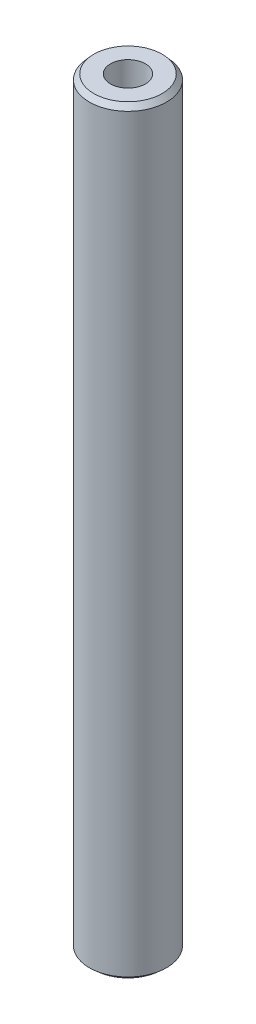
SolidWorks part; units mm, degrees
ref_plane "Front Plane" through (0, 0, 0) normal (0, 0, 1) x (1, 0, 0)
ref_plane "Top Plane" through (0, 0, 0) normal (0, 1, 0) x (1, 0, 0)
ref_plane "Right Plane" through (0, 0, 0) normal (1, 0, 0) x (0, 0, -1)
sketch "Sketch1" plane through (0, 0, 0) normal (0, 1, 0) x (1, 0, 0)
  circle A0 centre (0, 0) radius 5
  dimension "SHAFT_OD" = 10
extrude "Boss-Extrude1" add sketch "Sketch1" along normal blind 98.2793
sketch "Sketch2" plane through (0, 0, 0) normal (0, 1, 0) x (1, 0, 0)
  circle A0 centre (0, 0) radius 2.2611
  dimension "BORE_D" = 4.5222
extrude "Cut-Extrude1" cut sketch "Sketch2" along normal through all
chamfer "Chamfer1" distance 0.663 angle 41.206 2 edges at (0, 98.2793, 5) (0, 0, 5) first distance on face at (0, 98.2793, 5) first distance on face at (0, 0, 2.2611)
